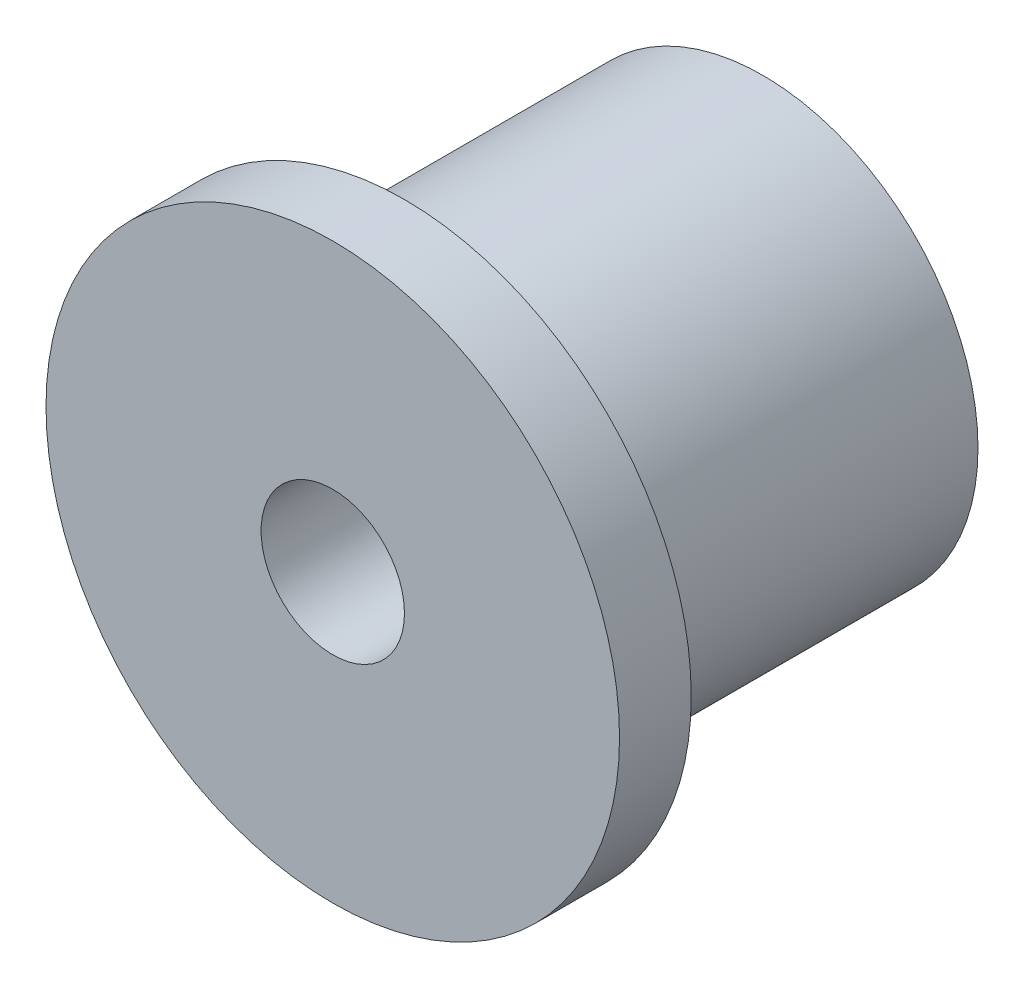
SolidWorks part; units mm, degrees
ref_plane "Front Plane" through (0, 0, 0) normal (0, 0, 1) x (1, 0, 0)
ref_plane "Top Plane" through (0, 0, 0) normal (0, 1, 0) x (1, 0, 0)
ref_plane "Right Plane" through (0, 0, 0) normal (1, 0, 0) x (0, 0, -1)
sketch "Sketch1" plane through (0, 0, 0) normal (0, 0, 1) x (1, 0, 0)
  circle A0 centre (0, 0) radius 100
  circle A1 centre (0, 0) radius 25
  circle A2 centre (0, 0) radius 75
  dimension "D1" = 200
  dimension "D2" = 50
  dimension "D3" = 150
extrude "Boss-Extrude2" add sketch "Sketch1" along normal blind 25 contours A0 A2 | A2 A1 region at (-97.1716, 0, 0) region at (-72.8787, 0, 0)
extrude "Boss-Extrude3" add sketch "Sketch1<4>" against normal blind 125 contours A2 A1 region at (-72.8787, 0, 0)
sketch "Sketch1<4>" plane through (0, 0, 0) normal (0, 0, 1) x (1, 0, 0) same geometry as "Sketch1"
